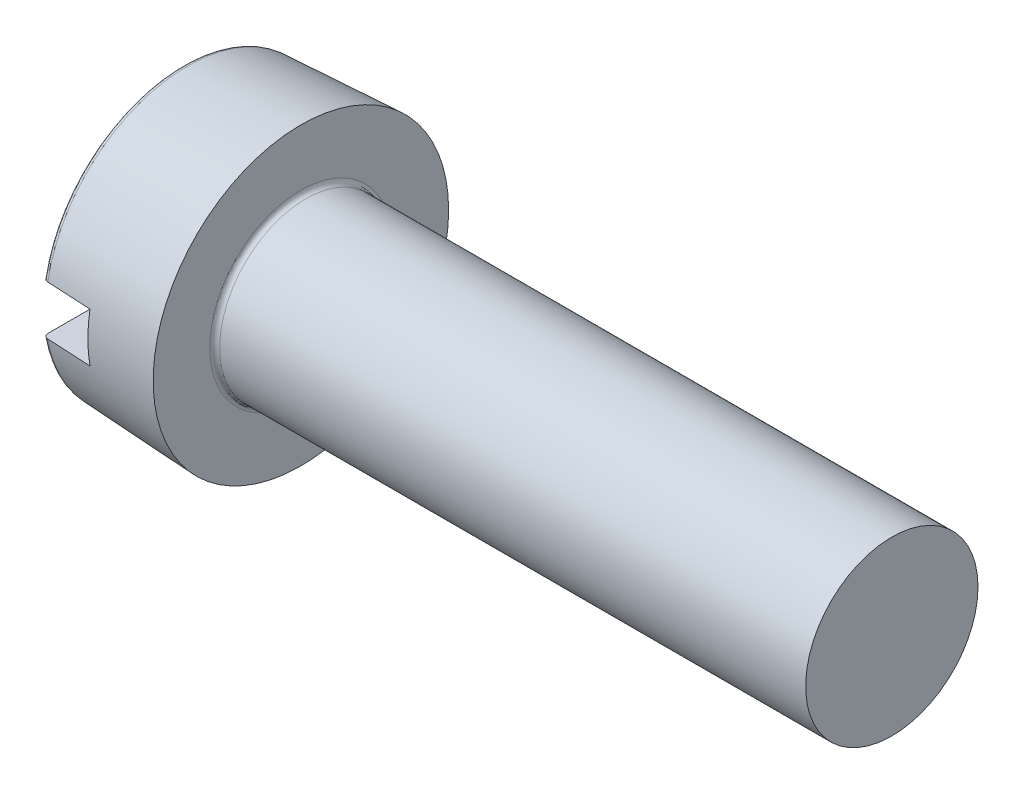
SolidWorks part; units mm, degrees
ref_plane "Front" through (0, 0, 0) normal (0, 0, 1) x (1, 0, 0)
ref_plane "Top" through (0, 0, 0) normal (0, 1, 0) x (1, 0, 0)
ref_plane "Right" through (0, 0, 0) normal (1, 0, 0) x (0, 0, -1)
ref_plane "Plane1" through (2.4, 0, 0) normal (1, 0, 0) x (0, 0, -1)
sketch "Sketch2" plane through (2.4, 0, 0) normal (1, 0, 0) x (0, 0, -1)
  circle A0 centre (0, 0) radius 3
  dimension "dk" = 6
extrude "BaseHead" add sketch "Sketch2" against normal blind 2.4 draft 3
sketch "Sketch3" plane through (2.4, -1.1101, -1.3544) normal (1, 0, 0) x (0, 0, -1)
  line L0 (-1.3544, 1.1101) -> (-0.1544, 1.1101) construction
  circle A0 centre (-1.3544, 1.1101) radius 1.75
  circle A1 centre (-1.3544, 1.1101) radius 3 construction
extrude "BaseBody" add sketch "Sketch3" along normal blind 12
cosmetic thread "ThreadCosmetic1" [suppressed] parameters "D1"=10.8, "D2"=2.85
sketch "Sketch4" plane through (-1.9, -1.9, 0) normal (0, 0, 1) x (0, 1, 0)
  line L1 (1.4, -1.9) -> (2.4, -1.9)
  line L2 (1.4, -1.9) -> (1.4, -2.9)
  line L3 (1.4, -2.9) -> (2.4, -2.9)
  line L4 (2.4, -1.9) -> (2.4, -2.9)
  line L5 (4.7742, -1.9) -> (-0.9742, -1.9) construction
  dimension "t" = 1
  dimension "m" = 0.5
extrude "Slot" cut sketch "Sketch4" against normal through all and the other way through all
fillet "HeadFillet" radius 0.1 3 edges at (2.4, 0, -1.75) (0, -2.8742, 0) (0, 2.8742, 0)
sketch "Sketch1" plane through (0, 0, 0) normal (0, 0, 1) x (1, 0, 0)
  line L0 (5.5483, 0) -> (-2.9147, 0) construction
  line L1 (2.4, 6.555) -> (-23.6, 6.555)
  line L2 (2.4, 6.555) -> (2.4, 1.555)
  line L3 (2.4, 1.555) -> (-25.1, 1.555)
  line L8 (-23.6, 1.75) -> (-25.1, 1.555)
  line L9 (-23.6, 6.555) -> (-23.6, 1.75)
  line L10 (2.4, -3) -> (2.4, 3) construction
  line L11 (14.4, -1.75) -> (14.4, 1.75) construction
  line L12 (14.4, 1.75) -> (2.5, 1.75) construction
  dimension "b1" = 3.11
  dimension "b" = 38
  dimension "x" = 1.5
  dimension "dd" = 5
sketch "Sketch5" plane through (0, 0, 0) normal (0, 0, 1) x (1, 0, 0)
  line L0 (14.5625, 1.75) -> (14.5625, 2.075)
  line L1 (14.5625, 2.075) -> (14.2375, 2.075)
  line L2 (14.2375, 2.075) -> (14.2375, 1.75)
  line L3 (14.2375, 1.75) -> (14.4, 1.4685)
  line L4 (14.4, 1.4685) -> (14.5625, 1.75)
  line L5 (14.4, -1.75) -> (14.4, 1.75) construction
  line L6 (0, 0) -> (15.9087, 0) construction
  dimension "D1" = 3.5
  dimension "D2" = 0.325
revolve "Cut-Revolve10" [suppressed] cut sketch "Sketch5" angle 360 about L6
pattern_linear "LPattern10" [suppressed] count 28 spacing 0.39 along (-1, 0, 0) of bodies 105
equation "\"m@Sketch4\" = \"n@Sketch4\" / 2"
equation "\"D1@Plane1\"=\"k@BaseHead\""
equation "\"D1@Sketch5\" = \"d@Sketch3\""
equation "\"D2@Sketch5\" =  ( \"d@Sketch3\" - \"D2@ThreadCosmetic1\" )  / 2"
equation "\"D3@LPattern10\" = \"D2@Sketch5\" * 1.2"
equation "\"D1@LPattern10\" = \"D1@ThreadCosmetic1\" / \"D3@LPattern10\""
